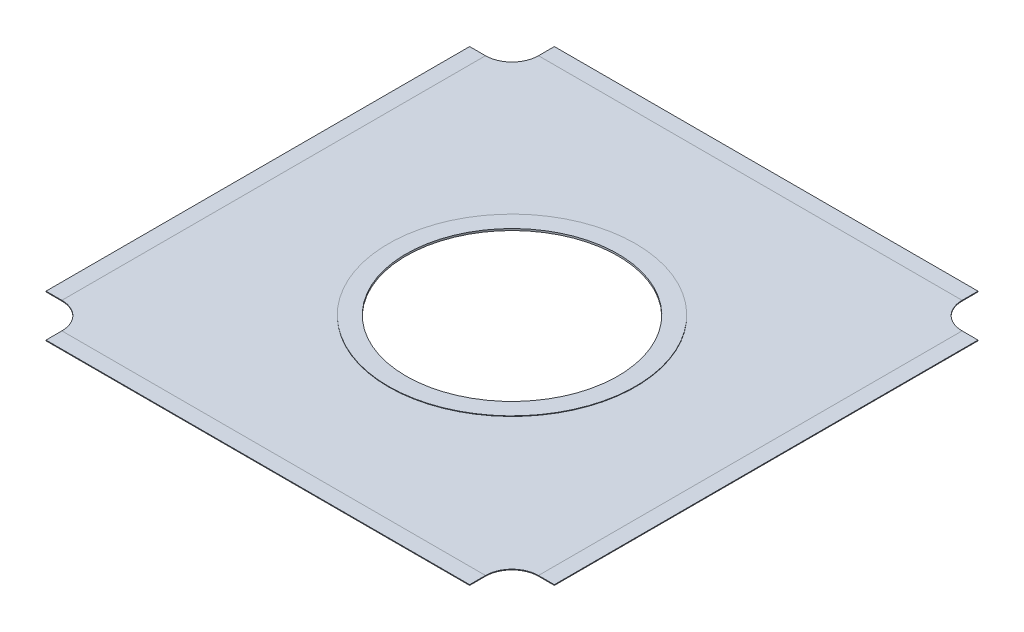
SolidWorks part; units mm, degrees
material "7050-T73510"
ref_plane "Front Plane" through (0, 0, 0) normal (0, 0, 1) x (1, 0, 0)
ref_plane "Top Plane" through (0, 0, 0) normal (0, 1, 0) x (1, 0, 0)
ref_plane "Right Plane" through (0, 0, 0) normal (1, 0, 0) x (0, 0, -1)
sketch "Sketch1" plane through (0, 0, 0) normal (0, 1, 0) x (1, 0, 0)
  line L0 (-152.4, -171.45) -> (-152.4, -182.88)
  line L1 (-152.4, 182.88) -> (152.4, 182.88)
  line L2 (-152.4, 182.88) -> (-152.4, 171.45)
  line L3 (-152.4, -182.88) -> (152.4, -182.88)
  line L4 (152.4, 182.88) -> (152.4, 171.45)
  line L5 (171.45, 152.4) -> (182.88, 152.4)
  line L7 (171.45, -152.4) -> (182.88, -152.4)
  line L8 (182.88, 152.4) -> (182.88, -152.4)
  line L9 (-171.45, 152.4) -> (-182.88, 152.4)
  line L11 (-171.45, -152.4) -> (-182.88, -152.4)
  line L12 (-182.88, 152.4) -> (-182.88, -152.4)
  line L13 (152.4, -171.45) -> (152.4, -182.88)
  circle A0 centre (0, 0) radius 88.9
  circle A1 centre (0, 0) radius 76.2
  arc A2 (-152.4, -171.45) -> (-171.45, -152.4) centre (-171.45, -171.45) ccw
  arc A3 (152.4, -171.45) -> (171.45, -152.4) centre (171.45, -171.45) cw
  arc A4 (171.45, 152.4) -> (152.4, 171.45) centre (171.45, 171.45) cw
  arc A5 (-171.45, 152.4) -> (-152.4, 171.45) centre (-171.45, 171.45) ccw
  point P18 (182.88, 0)
  point P19 (-182.88, 0)
  point P21 (0, 182.88)
  point P27 (152.4, 152.4)
  point P30 (-152.4, 152.4)
  dimension "D1" = 152.4
  dimension "D9" = 19.05
  dimension "D2" = 12.7
  dimension "D3" = 304.8
  dimension "D4" = 365.76
  dimension "D5" = 304.8
  dimension "D6" = 304.8
  dimension "D7" = 30.48
  dimension "D8" = 30.48
extrude "Boss-Extrude1" add sketch "Sketch1" along normal mid plane 0.508 contours L4 L1 L2 L3 A0 | L9 L12 L11 L2 | L8 L5 L4 L7 region at (-154.322, 0, 154.322)
extrude "Boss-Extrude2" add sketch "Sketch1<4>" along normal mid plane 1.27 separate body contours A0 A1 region at (-86.3855, 0, 0)
sketch "Sketch1<4>" plane through (0, 0, 0) normal (0, 1, 0) x (1, 0, 0) same geometry as "Sketch1"
ref_plane "Plane1" through (-171.45, 0, 0) normal (-1, 0, 0) x (0, 0, 1)
split line "Split Line1"
ref_plane "Plane3" through (171.45, 0, 0) normal (-1, 0, 0) x (0, 0, 1)
ref_plane "Plane4" through (0, 0, 171.45) normal (0, 0, -1) x (-1, 0, 0)
ref_plane "Plane2" through (0, 0, -171.45) normal (0, 0, 1) x (1, 0, 0)
split line "Split Line2"
split line "Split Line3"
split line "Split Line4"
equation "\"b\"=12"
equation "\"t\"=0.02"
equation "\"h\"=0.05"
equation "\"x\"=1.2"
equation "\"r\"= 0.75"
equation "\"d\"=6"
equation "\"w\"=0.5"
equation "\"D1@Sketch1\"=\"d\""
equation "\"D2@Sketch1\"=\"w\""
equation "\"D3@Sketch1\"=\"b\""
equation "\"D4@Sketch1\"=\"b\"+2*\"x\""
equation "\"D5@Sketch1\"=\"b\""
equation "\"D6@Sketch1\"=\"b\""
equation "\"D7@Sketch1\"=\"x\""
equation "\"D8@Sketch1\"=\"x\""
equation "\"D1@Boss-Extrude1\"=\"t\""
equation "\"D1@Boss-Extrude2\"=\"h\""
